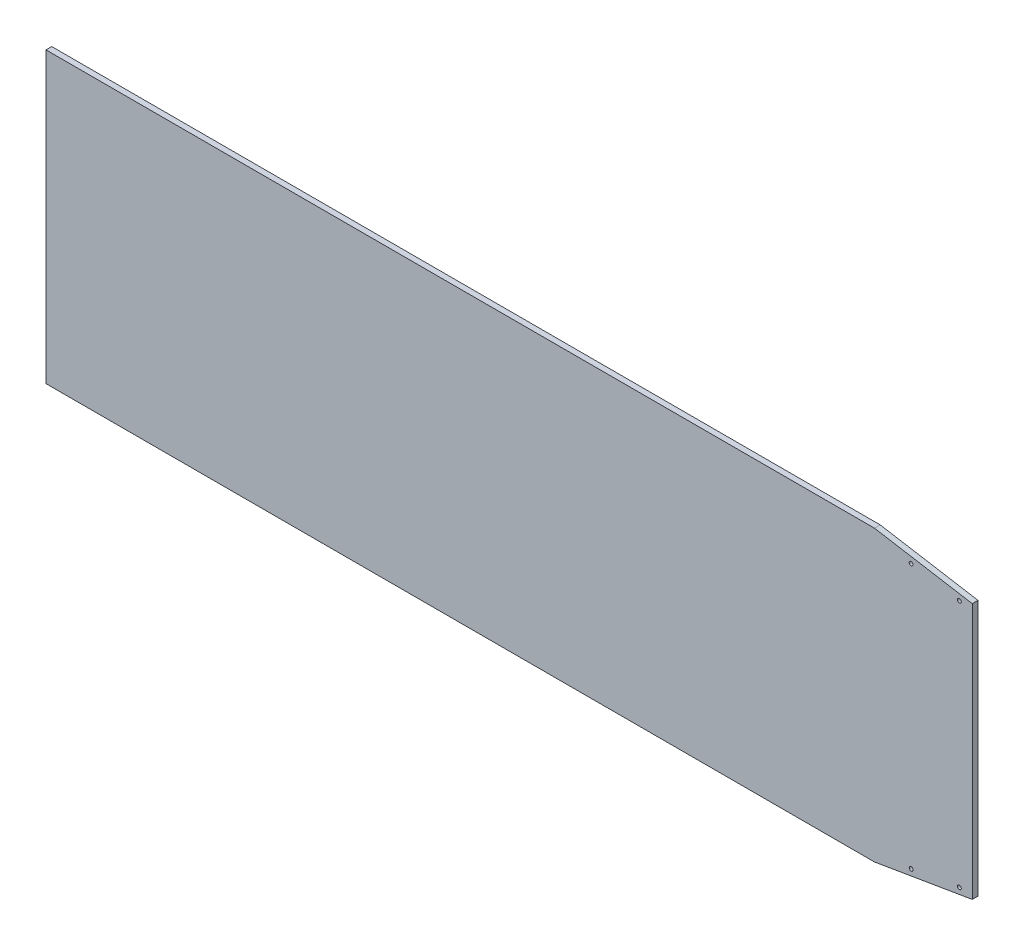
SolidWorks part; units mm, degrees
material "Pine"
ref_plane "Front Plane" through (0, 0, 0) normal (0, 0, 1) x (1, 0, 0)
ref_plane "Top Plane" through (0, 0, 0) normal (0, 1, 0) x (1, 0, 0)
ref_plane "Right Plane" through (0, 0, 0) normal (1, 0, 0) x (0, 0, -1)
sketch "Sketch1" plane through (0, 0, 0) normal (0, 0, 1) x (1, 0, 0)
  line L0 (-790.3617, 230.8882) -> (930.4883, 230.8882) construction
  line L1 (-790.3617, 230.8882) -> (930.4883, 230.8882)
  line L2 (-790.3617, 230.8882) -> (-790.3617, -369.5868)
  line L3 (-790.3617, -369.5868) -> (930.4883, -369.5868)
  line L4 (1133.6883, 196.7157) -> (1133.6883, -335.4143)
  line L5 (930.4883, 230.8882) -> (1133.6883, 196.7157)
  line L6 (1133.6883, -69.3493) -> (714.8177, -69.3493) construction
  line L7 (930.4883, -369.5868) -> (1133.6883, -335.4143)
  dimension "D1" = 532.13
  dimension "D2" = 1924.05
  dimension "D3" = 1720.85
extrude "Boss-Extrude1" add sketch "Sketch1" along normal blind 11.9062
hole_wizard "5/16 (0.3125) Diameter Hole1" positions "Sketch2" profile "Sketch3" hole size "5/16" standard "ANSI Inch" end condition through all
sketch "Sketch2" plane through (0, 0, 11.9062) normal (0, 0, 1) x (1, 0, 0)
  line L0 (930.4883, -369.5868) -> (1133.6883, -335.4143) construction
  line L1 (1133.6883, 196.7157) -> (930.4883, 230.8882) construction
  point P0 (1006.6883, -343.8938)
  point P2 (1106.8814, -327.0441)
  point P4 (1006.6883, 205.1952)
  point P6 (1106.8814, 188.3455)
  dimension "D1" = 12.7
  dimension "D2" = 12.7
  dimension "D3" = 76.2
  dimension "D4" = 101.6
  dimension "D5" = 12.7
  dimension "D6" = 12.7
sketch "Sketch3" plane through (1006.6883, -343.8938, 11.9062) normal (1, 0, 0) x (0, -1, 0)
  line L0 (0, 0) -> (0, 11.9062)
  line L1 (0, 11.9062) -> (3.9687, 11.9062)
  line L2 (3.9687, 11.9062) -> (3.9687, 0)
  line L5 (3.9687, 0) -> (0, 0)
  line L11 (0, -6.35) -> (0, 107.95) construction
  dimension "Thru Hole Dia." = 7.9375
  dimension "Thru Hole Depth" = 11.9062
